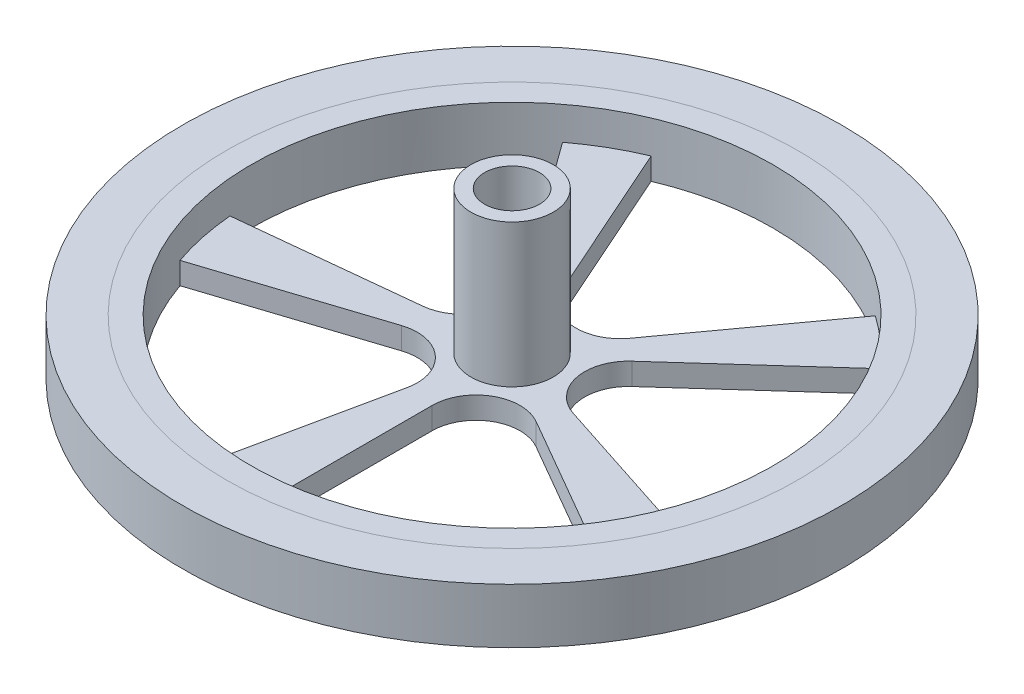
SolidWorks part; units mm, degrees
ref_plane "Front Plane" through (0, 0, 0) normal (0, 0, 1) x (1, 0, 0)
ref_plane "Top Plane" through (0, 0, 0) normal (0, 1, 0) x (1, 0, 0)
ref_plane "Right Plane" through (0, 0, 0) normal (1, 0, 0) x (0, 0, -1)
sketch "Sketch1" plane through (0, 0, 0) normal (0, 0, 1) x (1, 0, 0)
  line L0 (38.1, 6.35) -> (38.1, 0)
  line L1 (55, 0) -> (-55, 0) construction
  line L2 (38.1, 0) -> (0, 0)
  line L3 (0, 0) -> (0, 6.35)
  line L4 (0, -55) -> (0, 55) construction
  line L5 (0, 6.35) -> (3.175, 6.35)
  line L6 (3.175, 6.35) -> (3.175, 19.05)
  line L7 (3.175, 19.05) -> (4.7625, 19.05)
  line L8 (4.7625, 19.05) -> (4.7625, 2.54)
  line L9 (4.7625, 2.54) -> (30.1625, 2.54)
  line L10 (30.1625, 2.54) -> (30.1625, 6.35)
  line L11 (30.1625, 6.35) -> (38.1, 6.35)
  point P16 (3.9688, 19.05)
  dimension "D1" = 38.1
  dimension "D2" = 25.4
  dimension "D3" = 6.35
  dimension "D4" = 19.05
  dimension "D5" = 4.7625
  dimension "D6" = 3.175
  dimension "D7" = 12.7
  dimension "D8" = 2.54
revolve "Revolve1" add sketch "Sketch1" angle 360 about L3
ref_axis "Axis1" through (0, -1.4287, 0) along (0, 1, 0)
sketch "Sketch2" plane through (0, 0, 0) normal (0, -1, 0) x (1, 0, 0)
  line L0 (0.5991, 30.1565) -> (0.5991, 9.8365)
  line L1 (25.8168, 15.5971) -> (8.2191, 5.4371)
  arc A0 (0.5991, 30.1565) -> (25.8168, 15.5971) centre (0, 0) cw
  circle A1 centre (0, 0) radius 30.1625 construction
  circle A2 centre (0, 0) radius 30.1625 construction
  arc A3 (0.5991, 9.8365) -> (8.2191, 5.4371) centre (5.6791, 9.8365) ccw
  dimension "D3" = 5.08
  dimension "D1" = 60
  dimension "D2" = 20.32
extrude "Cut-Extrude1" cut sketch "Sketch2" against normal through all contours A3 L1 A0 L0
pattern_circular "CirPattern1" count 5 over 360 about axis through (0, -1.4287, 0) along (0, 1, 0) of "Cut-Extrude1"
sketch "Sketch4" plane through (0, 0, 0) normal (0, -1, 0) x (1, 0, 0)
  circle A0 centre (0, 0) radius 33.02
  circle A1 centre (0, 0) radius 38.1 construction
  dimension "D1" = 5.08
split line "Split Line1"
